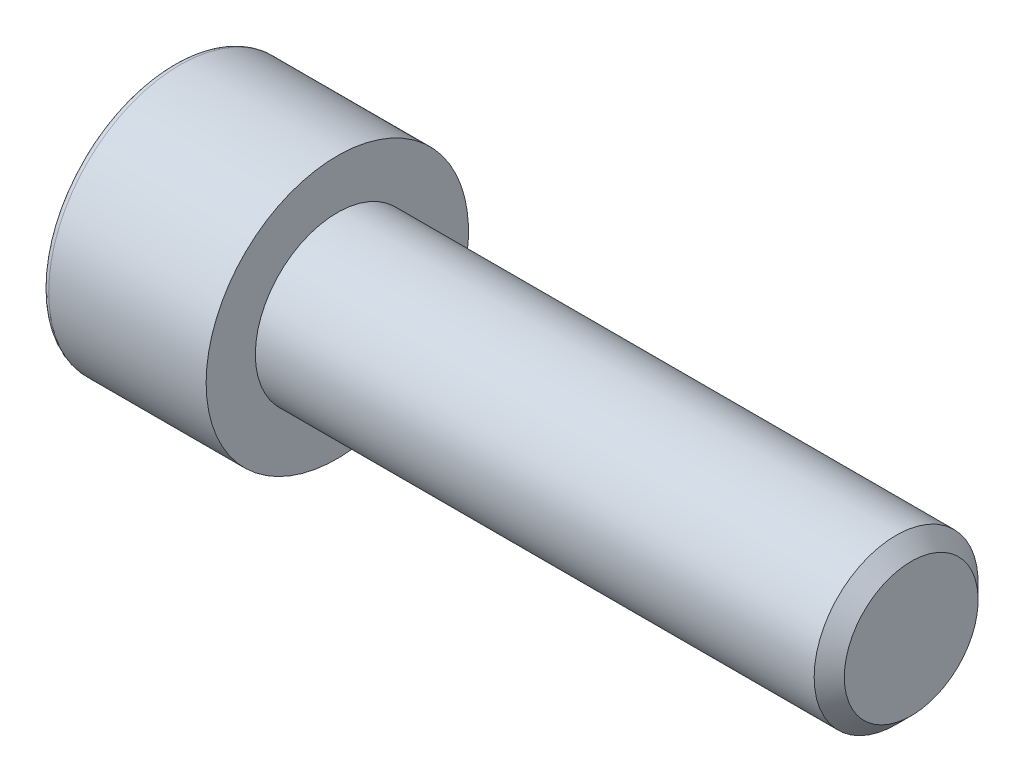
SolidWorks part; units mm, degrees
ref_plane "Płaszczyzna przednia" through (0, 0, 0) normal (0, 0, 1) x (1, 0, 0)
ref_plane "Płaszczyzna górna" through (0, 0, 0) normal (0, 1, 0) x (1, 0, 0)
ref_plane "Płaszczyzna prawa" through (0, 0, 0) normal (1, 0, 0) x (0, 0, -1)
sketch "Szkic1" plane through (0, 0, 0) normal (0, 0, 1) x (1, 0, 0)
  line L0 (0, 0) -> (0, 8)
  line L1 (0, 8) -> (10, 8)
  line L2 (10, 8) -> (10, 0)
  line L3 (10, 0) -> (0, 0)
  line L4 (10, 0) -> (0, 0) construction
revolve "Obrót1" add sketch "Szkic1" angle 360 about L4 reverse direction yes
sketch "Szkic2" plane through (0, 0, 0) normal (0, 0, 1) x (1, 0, 0)
  line L0 (0, 8) -> (0, 7.6)
  line L1 (0.4, 8) -> (0, 8)
  line L2 (10, 0) -> (0, 0) construction
  arc A0 (0, 7.6) -> (0.4, 8) centre (0.4, 7.6) cw
revolve "Wycięcie-obrót1" cut sketch "Szkic2" angle 360 about L2 reverse direction yes
sketch "Szkic3" plane through (0, 0, 0) normal (0, 0, 1) x (1, 0, 0)
  line L0 (10, 0) -> (10, 5)
  line L1 (10, 5) -> (44.08, 5)
  line L2 (44.08, 5) -> (45, 4.08)
  line L3 (45, 4.08) -> (45, 0)
  line L4 (45, 0) -> (10, 0)
  line L5 (45, 0) -> (10, 0) construction
revolve "Obrót2" add sketch "Szkic3" angle 360 about L5 reverse direction yes
cosmetic thread "Oznaczenie gwintu1" parameters "D1"=32, "D2"=8.16
sketch "Szkic4" plane through (0, 0, 0) normal (0, 0, 1) x (1, 0, 0)
  line L0 (0, 0) -> (0, 5.5)
  line L1 (0, 5.5) -> (5, 5.5)
  line L2 (5, 5.5) -> (8.1754, 0)
  line L3 (8.1754, 0) -> (0, 0)
  line L4 (8.1754, 0) -> (0, 0) construction
revolve "Wycięcie-obrót2" cut sketch "Szkic4" angle 360 about L4 reverse direction yes
sketch "Szkic5" plane through (0, 0, 0) normal (1, 0, 0) x (0, 0, -1)
  line L0 (-4, 2.3094) -> (-4, -2.3094)
  line L1 (-4, -2.3094) -> (0, -4.6188)
  line L2 (0, -4.6188) -> (4, -2.3094)
  line L3 (4, -2.3094) -> (4, 2.3094)
  line L4 (4, 2.3094) -> (0, 4.6188)
  line L5 (0, 4.6188) -> (-4, 2.3094)
  circle A0 centre (0, 0) radius 6
extrude "Dodanie-wyciągnięcie1" add sketch "Szkic5" along normal blind 7.5
ref_plane "Płaszczyzna1" through (10, 0, 0) normal (1, 0, 0) x (0, 0, -1)
ref_plane "IP2 XY" through (10, 0, 0) normal (-1, 0, 0) x (0, 0, 1)
ref_plane "IP2 XZ" through (0, 0, 0) normal (0, 1, 0) x (1, 0, 0)
ref_plane "IP2 YZ" through (0, 0, 0) normal (0, 0, -1) x (-1, 0, 0)
ref_axis "IP2 X" through (10, 0, 80.9) along (0, 0, -1)
ref_axis "IP2 Y" through (10, 50, 0) along (0, -1, 0)
ref_axis "IP2 Z" through (-80.9, 0, 0) along (1, 0, 0)
sketch3d "IP2"
  point P0 (10, 0, 0)
